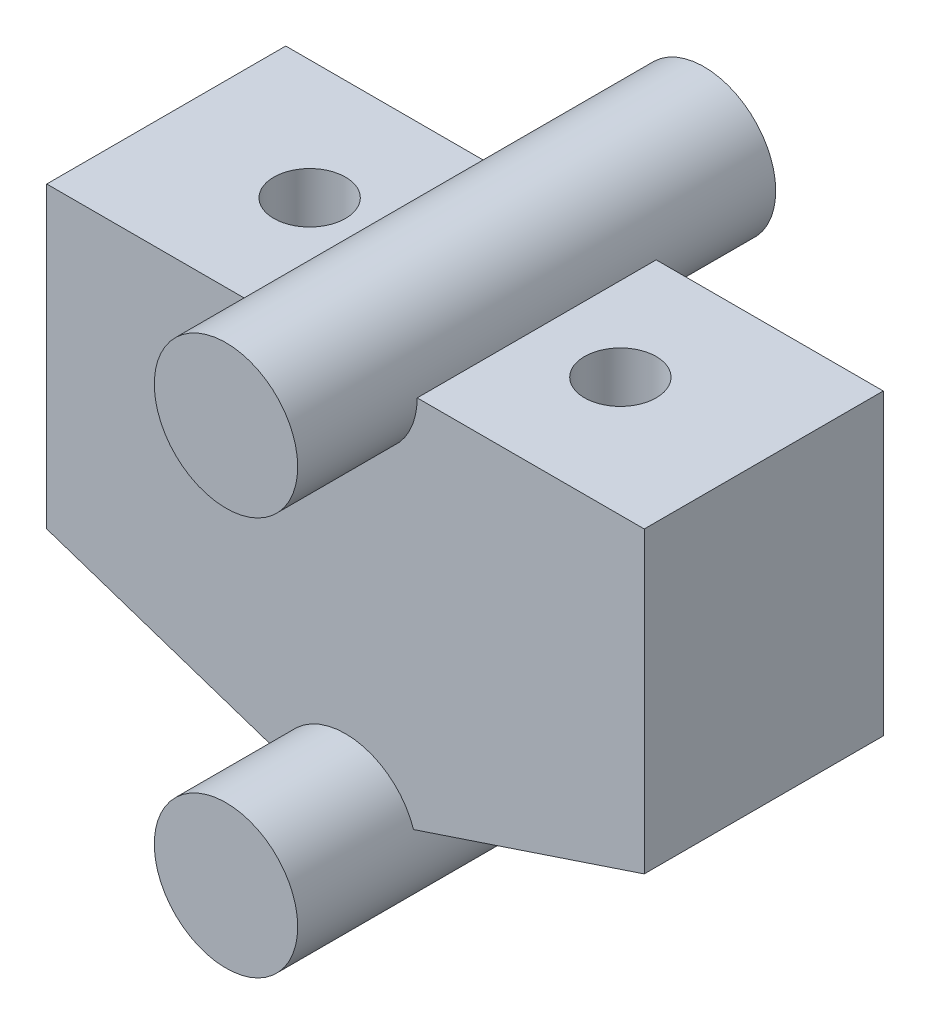
SolidWorks part; units mm, degrees
ref_plane "Front Plane" through (0, 0, 0) normal (0, 0, 1) x (1, 0, 0)
ref_plane "Top Plane" through (0, 0, 0) normal (0, 1, 0) x (1, 0, 0)
ref_plane "Right Plane" through (0, 0, 0) normal (1, 0, 0) x (0, 0, -1)
sketch "Sketch1" plane through (0, 0, 0) normal (0, 0, 1) x (1, 0, 0)
  line L0 (-12.5, -6.25) -> (-2.846, -9.468)
  line L1 (-12.5, 6.25) -> (12.5, 6.25)
  line L2 (-12.5, 6.25) -> (-12.5, -6.25)
  line L4 (12.5, 6.25) -> (12.5, -6.25)
  line L5 (-12.5, 6.25) -> (12.5, -6.25) construction
  line L6 (-12.5, -6.25) -> (12.5, 6.25) construction
  line L7 (2.846, -9.468) -> (12.5, -6.25)
  line L8 (-12.5, -6.25) -> (0, -10.4167) construction
  circle A0 centre (0, -10.4167) radius 3
  point P0 (0, 0)
  dimension "D4" = 6
  dimension "D1" = 12.5
  dimension "D2" = 25
  dimension "D3" = 16.6667
extrude "Boss-Extrude1" add sketch "Sketch1" along normal blind 10 contours A0 L7 L4 L1 L2 L0 region at (0, -0.8429, 0)
extrude "Boss-Extrude2" add sketch "Sketch1<3>" along normal blind 15 and the other way blind 5 contours A0 region at (0, -10.4167, 0)
sketch "Sketch1<3>" plane through (0, 0, 0) normal (0, 0, 1) x (1, 0, 0) same geometry as "Sketch1"
sketch "Sketch2" plane through (0, 6.25, 0) normal (0, 1, 0) x (1, 0, 0)
  line L0 (-12.5, 0) -> (12.5, 0) construction
  line L1 (-12.5, -10) -> (-12.5, 0) construction
  line L2 (0, -55) -> (0, 55) construction
  circle A0 centre (-6.5, -5) radius 1.5
  circle A1 centre (6.5, -5) radius 1.5
  dimension "D1" = 3
  dimension "D2" = 5
  dimension "D3" = 6
extrude "Cut-Extrude1" cut sketch "Sketch2" against normal through all
sketch "Sketch3" plane through (0, 0, 10) normal (0, 0, 1) x (1, 0, 0)
  line L0 (-12.5, 6.25) -> (12.5, 6.25) construction
  circle A0 centre (0, 6.25) radius 3
  dimension "D1" = 6
extrude "Boss-Extrude3" add sketch "Sketch3" along normal blind 5 and the other way blind 15
